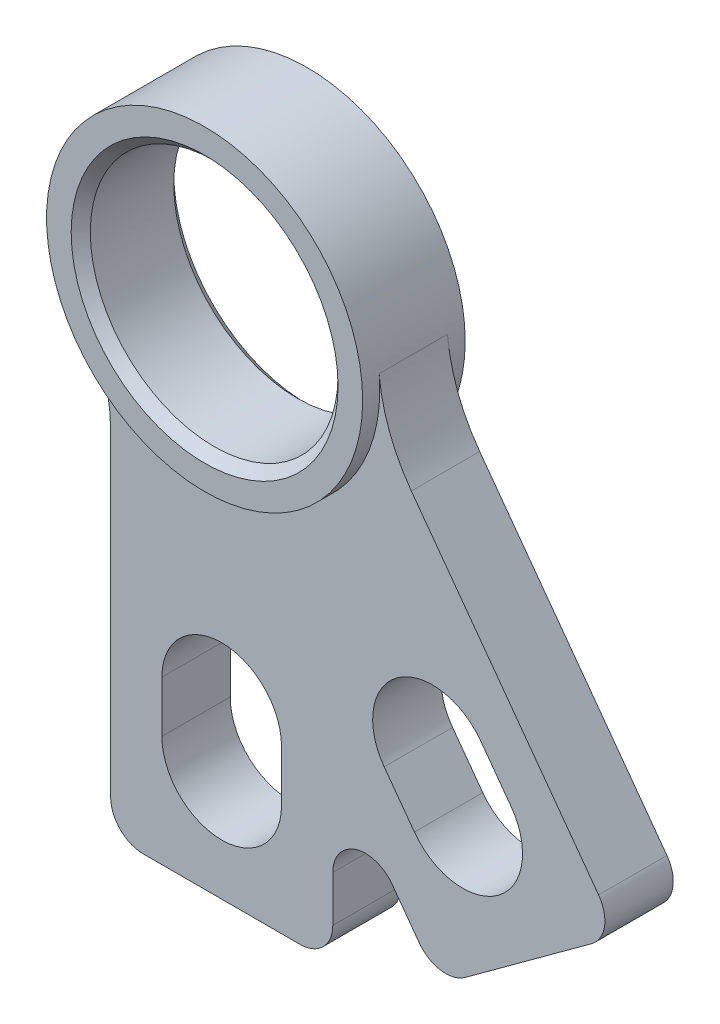
SolidWorks part; units mm, degrees
material "AISI 4130 Steel, annealed at 865C"
ref_plane "X-Y Datum" through (0, 0, 0) normal (0, 0, 1) x (1, 0, 0)
ref_plane "X-Z Datum" through (0, 0, 0) normal (0, 1, 0) x (1, 0, 0)
ref_plane "Y-Z Datum" through (0, 0, 0) normal (1, 0, 0) x (0, 0, -1)
sketch "Sketch1" plane through (0, 0, 0) normal (0, 0, 1) x (1, 0, 0)
  line L0 (0, -37.9413) -> (0, -33.1787) construction
  line L1 (-5.5562, -37.9413) -> (-5.5562, -33.1787)
  line L2 (5.5562, -37.9413) -> (5.5562, -33.1787)
  line L3 (22.3879, -30.632) -> (19.5777, -26.787) construction
  line L4 (17.902, -33.9106) -> (15.0918, -30.0656)
  line L5 (26.8737, -27.3535) -> (24.0635, -23.5085)
  line L6 (-10.3187, -15.7343) -> (-10.3187, -48.26)
  line L7 (-10.3187, -48.26) -> (10.3187, -48.26)
  line L10 (20.1457, -45.0517) -> (36.8075, -32.8742)
  line L11 (36.8075, -32.8742) -> (17.6152, -6.6144)
  line L13 (10.3187, -48.26) -> (10.3187, -31.606)
  line L14 (0, -43.4975) -> (0, -48.26) construction
  line L15 (25.6664, -35.1179) -> (28.4766, -38.9629) construction
  line L16 (25.4686, -25.431) -> (29.3137, -22.6208) construction
  line L17 (-5.5562, -35.56) -> (-10.3187, -35.56) construction
  line L18 (-10.3187, -22.86) -> (10.3187, -22.86) construction
  line L19 (10.3187, -22.86) -> (10.3187, -48.26) construction
  line L20 (5.5562, -35.56) -> (10.3187, -35.56) construction
  line L21 (0, -27.6225) -> (0, -22.86) construction
  line L22 (20.1457, -45.0517) -> (5.158, -24.5449) construction
  line L23 (5.158, -24.5449) -> (21.8198, -12.3674) construction
  line L24 (16.4969, -31.9881) -> (12.6519, -34.7983) construction
  line L25 (16.2991, -22.3012) -> (13.4889, -18.4561) construction
  line L29 (20.1457, -45.0517) -> (10.3187, -31.606)
  line L31 (219.5217, -300.3591) -> (0, 0) construction
  line L32 (0, -364.1414) -> (0, 0) construction
  circle A0 centre (0, 0) radius 11.5062
  arc A1 (-5.5562, -37.9413) -> (5.5562, -37.9413) centre (0, -37.9413) ccw
  arc A2 (5.5562, -33.1787) -> (-5.5562, -33.1787) centre (0, -33.1787) ccw
  arc A3 (17.902, -33.9106) -> (26.8737, -27.3535) centre (22.3879, -30.632) ccw
  arc A4 (24.0635, -23.5085) -> (15.0918, -30.0656) centre (19.5777, -26.787) ccw
  arc A5 (14.6215, 1.3227) -> (-12.5852, -7.5598) centre (0, 0) ccw
  arc A6 (17.6152, -6.6144) -> (14.6215, 1.3227) centre (30.4319, 2.7529) cw
  arc A7 (-10.3187, -15.7343) -> (-12.5852, -7.5598) centre (-26.1937, -15.7343) ccw
  arc A14 (-12.5852, -7.5598) -> (14.6215, 1.3227) centre (0, 0) ccw
  point P5 (0, -35.56)
  point P11 (20.9828, -28.7095)
  point P24 (28.4766, -38.9629)
  point P31 (0, -48.26)
  point P39 (25.6664, -35.1179)
  dimension "D1" = 23.0124
  dimension "D2" = 3.175
  dimension "D8" = 15.875
  dimension "D6" = 22.86
  dimension "D3" = 20.6375
  dimension "D4" = 4.7625
  dimension "D5" = 25.4
  dimension "D7" = 22.86
extrude "Boss-Extrude2" add sketch "Sketch1" along normal mid plane 9.525 contours A5 A14 A0 region at (-4.4276, 13.5615, 0)
extrude "Boss-Extrude3" add sketch "Sketch1<4>" along normal mid plane 6.35 contours A14 A7 L6 L7 L10 L11 A6 A4 L5 A3 L4 A2 L2 A1 L1 region at (8.9526, -27.4215, 0)
sketch "Sketch1<4>" plane through (0, 0, 0) normal (0, 0, 1) x (1, 0, 0) same geometry as "Sketch1"
fillet "Fillet1" radius 3.048 5 edges at (-10.3187, -48.26, 0) (36.8075, -32.8742, 0) (10.3187, -31.606, 0) (10.3187, -48.26, 0) (20.1457, -45.0517, 0)
chamfer "Chamfer1" distance 0.889 angle 45 2 edges at (11.5062, 0, -4.7625) (11.5062, 0, 4.7625)
sketch "Sketch2" plane through (0, 0, 3.175) normal (0, 0, 1) x (1, 0, 0)
  line L0 (12.4208, -38.0444) -> (0, 0) construction
  line L1 (0, 0) -> (-4.5564, 13.9562) construction
  line L2 (0, 0) -> (-10.938, -3.5711) construction
  arc A0 (15.8276, -39.1434) -> (10.3187, -40.9419) centre (13.3667, -40.9419) ccw construction
  circle A1 centre (0, 0) radius 14.6812 construction
  circle A2 centre (0, 0) radius 11.5062 construction
ref_plane "Plane1" through (0, 0, 0) normal (-0.3104, 0.9506, 0) x (0, 0, 1)
